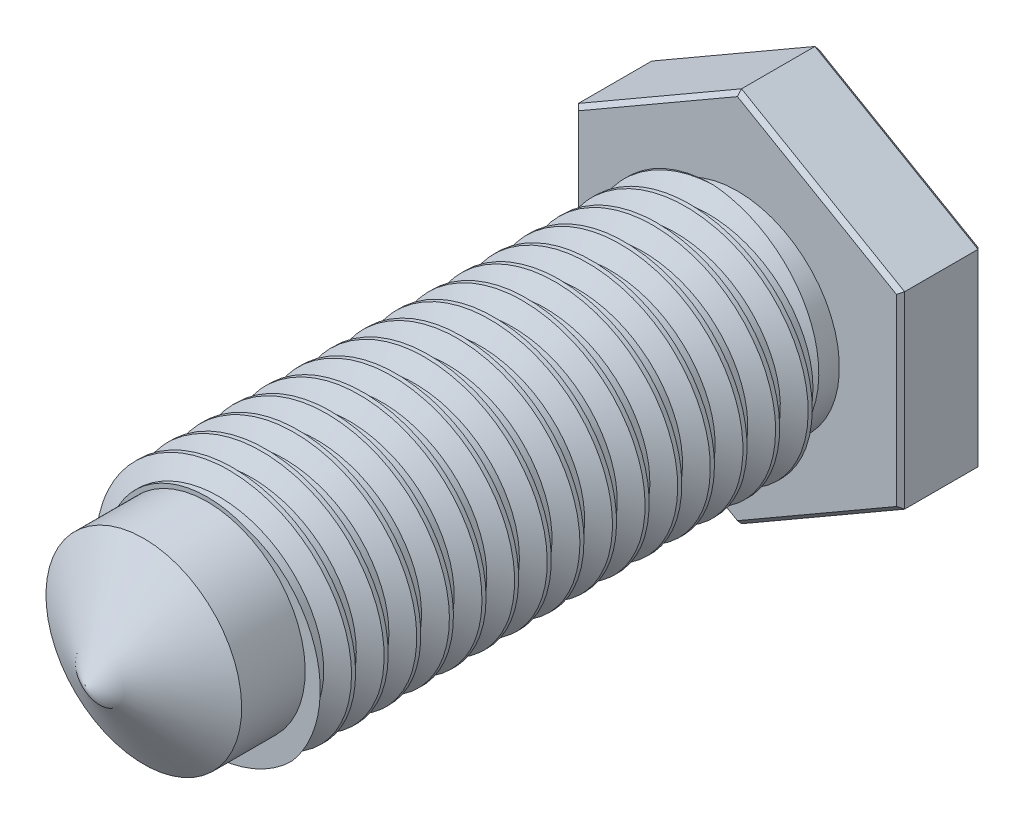
SolidWorks part; units mm, degrees
ref_plane "Front Plane" through (0, 0, 0) normal (0, 0, 1) x (1, 0, 0)
ref_plane "Top Plane" through (0, 0, 0) normal (0, 1, 0) x (1, 0, 0)
ref_plane "Right Plane" through (0, 0, 0) normal (1, 0, 0) x (0, 0, -1)
sketch "Sketch1" plane through (0, 0, 0) normal (1, 0, 0) x (0, 0, -1)
  line L0 (0, 0) -> (-18, 0) construction
  line L2 (-16.2377, 2.933) -> (-2.6, 2.933)
  line L3 (-2, 2.5) -> (-2, 5)
  line L4 (-2, 5) -> (0, 5)
  line L5 (0, 5) -> (0, 0)
  line L6 (0, 0) -> (-18, 0)
  line L7 (-18, 0) -> (-16.2377, 2.933)
  line L8 (-2, 2.5) -> (-2.6, 2.5)
  line L9 (-2.6, 2.5) -> (-2.6, 2.933)
  dimension "D1" = 18
  dimension "D2" = 59
  dimension "D3" = 10
  dimension "D4" = 5.866
  dimension "D5" = 0.6
  dimension "D6" = 5
revolve "Revolve1" add sketch "Sketch1" angle 360 about L0
thread "Thread1" pitch 0.8 profile "Thread Profile1" start angle 0, offset 2.7, length 28, pitch 0.8, diameter 5.866
ref_plane "Plane1" through (-2.933, 0, 2.7) normal (0, -1, 0) x (-1, 0, 0)
sketch "Thread Profile1" plane through (-2.933, 0, 2.7) normal (0, -1, 0) x (-1, 0, 0)
  line L0 (0, 0) -> (0, 0.8) construction
  line L11 (0, 0) -> (0, 0.7)
  line L12 (0, 0.7) -> (-0.433, 0.45)
  line L13 (-0.433, 0.45) -> (-0.433, 0.25)
  line L15 (-0.433, 0.25) -> (0, 0)
  line L17 (-0.433, 0.35) -> (0, 0.35) construction
  point P2 (0, 0)
  dimension "Pitch" = 0.8
  dimension "Profile_Angle" = 60
  dimension "Profile_Land" = 0.2
  dimension "Profile_Height" = 0.433
sketch "Sketch5" plane through (0, 0, 0) normal (0, 0, -1) x (-1, 0, 0)
  line L1 (0, 4.6188) -> (-4, 2.3094)
  line L2 (-4, 2.3094) -> (-4, -2.3094)
  line L3 (-4, -2.3094) -> (0, -4.6188)
  line L4 (0, -4.6188) -> (4, -2.3094)
  line L5 (4, -2.3094) -> (4, 2.3094)
  line L6 (4, 2.3094) -> (0, 4.6188)
  circle A0 centre (0, 0) radius 4 construction
  circle A1 centre (0, 0) radius 5.2104
  dimension "D1" = 8
ref_plane "Plane2" through (0, 0, 18) normal (0, 0, -1) x (-1, 0, 0)
extrude "Cut-Extrude1" cut sketch "Sketch5" against normal blind 10
chamfer "Chamfer1" distance 0.1 angle 45 12 edges at (-2, 3.4641, 2) (-4, 0, 2) (-2, -3.4641, 2) (2, -3.4641, 2) (4, 0, 2) (2, 3.4641, 2) (-2, 3.4641, 0) (-4, 0, 0) (-2, -3.4641, 0) (2, -3.4641, 0) (4, 0, 0) (2, 3.4641, 0)
sketch "Sketch7" plane through (0, 0, 18) normal (0, 0, -1) x (-1, 0, 0)
  circle A0 centre (0, 0) radius 2.4
  circle A1 centre (0, 0) radius 2.933
  dimension "D1" = 4.8
extrude "Cut-Extrude2" cut sketch "Sketch7" along normal blind 3
